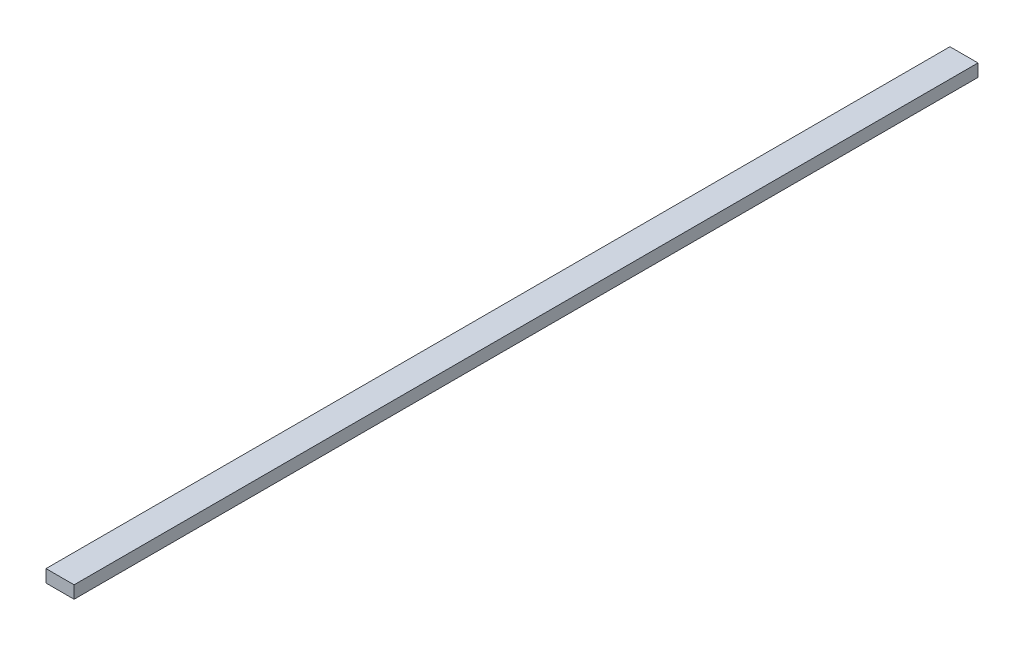
SolidWorks part; units mm, degrees
ref_plane "Front Plane" through (0, 0, 0) normal (1, 0, 0) x (0, 1, 0)
ref_plane "Top Plane" through (0, 0, 0) normal (0, 0, 1) x (0, 1, 0)
ref_plane "Right Plane" through (0, 0, 0) normal (0, 1, 0) x (-1, 0, 0)
sketch "Sketch1" plane through (0, 0, 0) normal (0, 0, 1) x (0, 1, 0)
  line L1 (-8.3312, -18.6436) -> (8.3312, -18.6436)
  line L2 (-8.3312, -18.6436) -> (-8.3312, 18.6436)
  line L3 (-8.3312, 18.6436) -> (8.3312, 18.6436)
  line L4 (8.3312, -18.6436) -> (8.3312, 18.6436)
  line L5 (-8.3312, -18.6436) -> (8.3312, 18.6436) construction
  line L6 (-8.3312, 18.6436) -> (8.3312, -18.6436) construction
  point P0 (0, 0)
  dimension "D1" = 16.6624
  dimension "D2" = 37.2872
extrude "Boss-Extrude1" add sketch "Sketch1" along normal mid plane 1200
